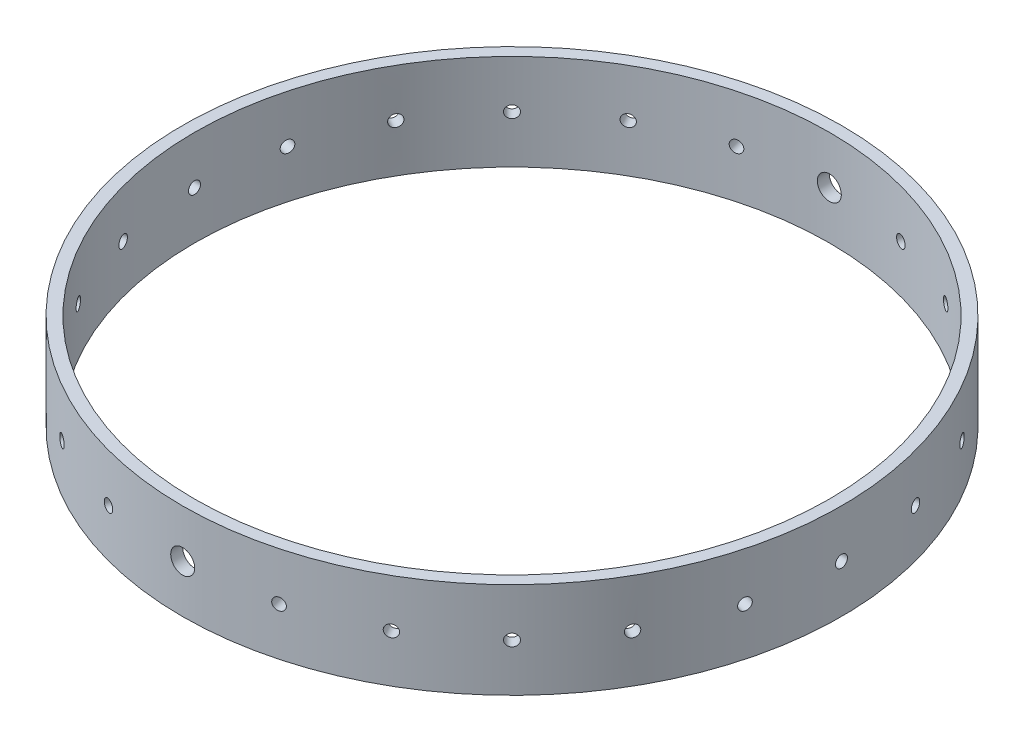
SolidWorks part; units mm, degrees
ref_plane "Front Plane" through (0, 0, 0) normal (0, 0, 1) x (1, 0, 0)
ref_plane "Top Plane" through (0, 0, 0) normal (0, 1, 0) x (1, 0, 0)
ref_plane "Right Plane" through (0, 0, 0) normal (1, 0, 0) x (0, 0, -1)
sketch "Sketch1" plane through (0, 0, 0) normal (0, 1, 0) x (1, 0, 0)
  circle A0 centre (0, 0) radius 87.3125
  circle A1 centre (0, 0) radius 84.1375
  dimension "D1" = 174.625
  dimension "D2" = 168.275
extrude "Boss-Extrude1" add sketch "Sketch1" along normal blind 25.4
ref_plane "Plane1" through (0, 0, 87.3125) normal (0, 0, 1) x (1, 0, 0)
sketch "Sketch2" plane through (0, 0, 87.3125) normal (0, 0, 1) x (1, 0, 0)
  line L0 (84.1375, 25.4) -> (-84.1375, 25.4) construction
  circle A0 centre (0, 12.7) radius 1.5875
  dimension "D1" = 3.175
  dimension "D2" = 12.7
extrude "Cut-Extrude1" cut sketch "Sketch2" against normal up to next
ref_axis "Axis1" through (0, 25.4, 0) along (0, -1, 0)
pattern_circular "CirPattern1" count 24 over 360 about axis through (0, 25.4, 0) along (0, -1, 0) of "Cut-Extrude1"
sketch "Sketch3" plane through (0, 0, 87.3125) normal (0, 0, 1) x (1, 0, 0)
  circle A0 centre (0, 12.7) radius 3.175
  dimension "D1" = 6.35
extrude "Cut-Extrude2" cut sketch "Sketch3" against normal through all both and the other way through all
ref_axis "Axis2" through (0, 12.7, 83.8984) along (0, 0, 1)
ref_plane "Plane2" through (0, 0, 84.1375) normal (0, 0, 1) x (1, 0, 0)
